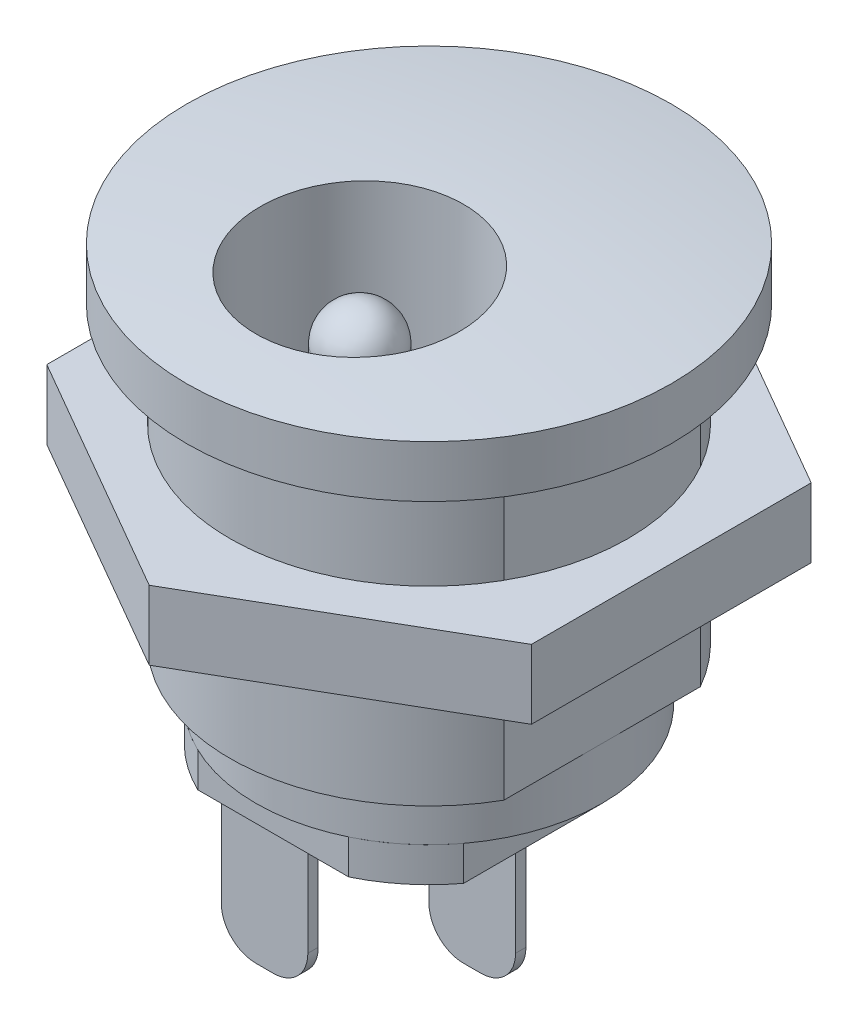
SolidWorks part; units mm, degrees
ref_plane "Front" through (0, 0, 0) normal (0, 0, 1) x (1, 0, 0)
ref_plane "Top" through (0, 0, 0) normal (0, 1, 0) x (1, 0, 0)
ref_plane "Right" through (0, 0, 0) normal (1, 0, 0) x (0, 0, -1)
sketch "Sketch1" plane through (0, 0, 0) normal (0, 1, 0) x (1, 0, 0)
  circle A0 centre (0, 0) radius 7
  dimension "D1" = 14
extrude "Boss-Extrude1" add sketch "Sketch1" along normal blind 1.5
dome "Dome1" faces to dome 1 distance 0.5 reverse direction no elliptical dome no face at (0, 1.5, 7) parameters "D1"=0.5
sketch "Sketch2" plane through (0, 0, 0) normal (0, -1, 0) x (1, 0, 0)
  circle A0 centre (0, 0) radius 5.75
  dimension "D1" = 11.5
extrude "Boss-Extrude2" add sketch "Sketch2" along normal blind 8.5
sketch "Sketch3" plane through (0, -8.5, 0) normal (0, -1, 0) x (1, 0, 0)
  circle A0 centre (0, 0) radius 5
  dimension "D1" = 10
extrude "Boss-Extrude3" add sketch "Sketch3" along normal blind 1.5
sketch "Sketch4" plane through (0, -8.5, 0) normal (0, -1, 0) x (1, 0, 0)
  line L0 (-5, 2.8395) -> (-5, -2.8395)
  line L1 (0, 0) -> (0, 7) construction
  line L2 (5, 2.8395) -> (5, -2.8395)
  circle A0 centre (0, 0) radius 5.75 construction
  arc A1 (-5, 2.8395) -> (-5, -2.8395) centre (0, 0) ccw
  circle A2 centre (0, 0) radius 5 construction
  circle A3 centre (0, 0) radius 7 construction
  arc A4 (5, 2.8395) -> (5, -2.8395) centre (0, 0) cw
extrude "Cut-Extrude1" cut sketch "Sketch4" against normal up to surface (8.5 mm away) up to face at (0, 0, -5.75)
sketch "Sketch5" plane through (0, -10, 0) normal (0, -1, 0) x (1, 0, 0)
  line L0 (-2.1794, 4.5) -> (2.1794, 4.5)
  line L1 (0, 4.5) -> (0, 0) construction
  line L2 (0, 0) -> (-5, 0) construction
  line L3 (-4, 3) -> (-4, -3)
  line L4 (4, 3) -> (4, -1)
  line L5 (-2.1794, -4.5) -> (2.1794, -4.5)
  line L6 (4, -1) -> (2.5, -1)
  line L7 (2.5, -1) -> (2.5, -4.3301)
  arc A2 (-4, -3) -> (-2.1794, -4.5) centre (0, 0) ccw
  arc A3 (-2.1794, 4.5) -> (-4, 3) centre (0, 0) ccw
  arc A4 (4, 3) -> (2.1794, 4.5) centre (0, 0) ccw
  arc A5 (5, 0) -> (-5, 0) centre (0, 0) ccw construction
  arc A8 (2.1794, -4.5) -> (2.5, -4.3301) centre (0, 0) ccw
  dimension "D1" = 9
  dimension "D2" = 8
  dimension "D3" = 6.5
  dimension "D4" = 5.5
extrude "Boss-Extrude5" add sketch "Sketch5" along normal blind 1 separate body
sketch "Sketch6" plane through (0, 0, 0) normal (0, -1, 0) x (1, 0, 0)
  circle A0 centre (0, 2) radius 3
  circle A1 centre (0, 0) radius 7 construction
  dimension "D1" = 6
  dimension "D2" = 2
extrude "Cut-Extrude2" cut sketch "Sketch6" against normal through all and the other way blind 8
sketch "Sketch7" plane through (0, -8, 0) normal (0, 1, 0) x (1, 0, 0)
  circle A0 centre (0, -2) radius 1.05
  dimension "D1" = 2.1
extrude "Boss-Extrude6" add sketch "Sketch7" along normal blind 8
dome "Dome2" faces to dome 1 distance 1.05 reverse direction no elliptical dome no face at (0, 0, 3.05) parameters "D1"=1.05
sketch "Sketch8" plane through (0, 0, 0) normal (0, -1, 0) x (1, 0, 0)
  line L1 (7, -4.0415) -> (7, 4.0415)
  line L2 (7, 4.0415) -> (0, 8.0829)
  line L3 (0, 8.0829) -> (-7, 4.0415)
  line L4 (-7, 4.0415) -> (-7, -4.0415)
  line L5 (-7, -4.0415) -> (0, -8.0829)
  line L6 (0, -8.0829) -> (7, -4.0415)
  circle A0 centre (0, 0) radius 7 construction
  circle A1 centre (0, 0) radius 5.75
  dimension "D1" = 14
extrude "Boss-Extrude7" add sketch "Sketch8" along normal blind 2 from offset 3 separate body
sketch "Sketch9" plane through (0, -11, 0) normal (0, -1, 0) x (1, 0, 0)
  line L0 (-4, 3) -> (-4, -3) construction
  line L1 (-2.5, 3.5) -> (0, 3.5)
  line L2 (-2.5, 3.5) -> (-2.5, 3.2)
  line L3 (-2.5, 3.2) -> (0, 3.2)
  line L4 (0, 3.5) -> (0, 3.2)
  line L5 (0.5, 0.5) -> (3, 0.5)
  line L6 (0.5, 0.5) -> (0.5, 0.2)
  line L7 (0.5, 0.2) -> (3, 0.2)
  line L8 (3, 0.5) -> (3, 0.2)
  line L9 (-3.5, -0.5) -> (-3.2, -0.5)
  line L10 (-3.5, -0.5) -> (-3.5, -3)
  line L11 (-3.5, -3) -> (-3.2, -3)
  line L12 (-3.2, -0.5) -> (-3.2, -3)
  line L13 (2.1794, 4.5) -> (-2.1794, 4.5) construction
  line L14 (4, -1) -> (4, 3) construction
  line L15 (-2.1794, -4.5) -> (2.1794, -4.5) construction
  dimension "D1" = 0.3
  dimension "D2" = 2.5
  dimension "D3" = 0.5
  dimension "D4" = 1
  dimension "D5" = 1
  dimension "D6" = 4
  dimension "D7" = 1.5
  dimension "D8" = 1.5
extrude "Boss-Extrude8" add sketch "Sketch9" along normal blind 4.5
fillet "Fillet1" radius 1 6 edges at (-3.35, -15.5, -3) (-3.35, -15.5, -0.5) (3, -15.5, 0.35) (0.5, -15.5, 0.35) (0, -15.5, 3.35) (-2.5, -15.5, 3.35)
